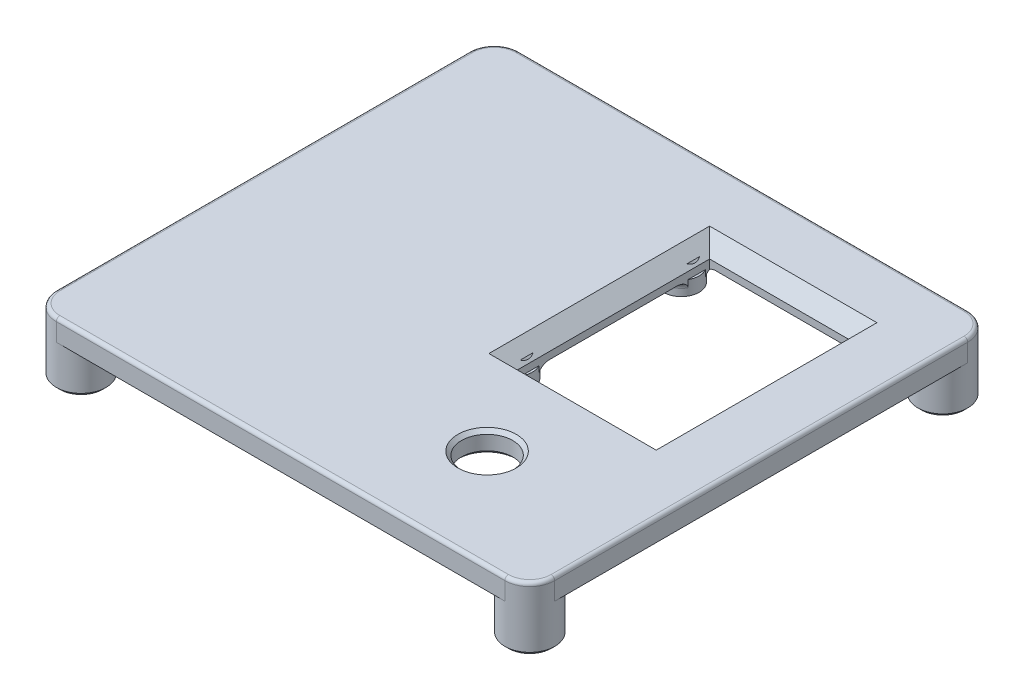
SolidWorks part; units mm, degrees
ref_plane "Front Plane" through (0, 0, 0) normal (0, 0, 1) x (1, 0, 0)
ref_plane "Top Plane" through (0, 0, 0) normal (0, 1, 0) x (1, 0, 0)
ref_plane "Right Plane" through (0, 0, 0) normal (1, 0, 0) x (0, 0, -1)
sketch "Sketch1" plane through (0, 0, 0) normal (0, 1, 0) x (1, 0, 0)
  line L1 (0, 0) -> (70, 0)
  line L2 (0, 0) -> (0, 65)
  line L3 (0, 65) -> (70, 65)
  line L4 (70, 0) -> (70, 65)
  dimension "D1" = 70
  dimension "D2" = 65
extrude "Boss-Extrude1" add sketch "Sketch1" along normal blind 3
fillet "Fillet1" radius 3.5 4 edges at (70, 1.5, -65) (70, 1.5, 0) (0, 1.5, 0) (0, 1.5, -65)
sketch "Sketch2" plane through (0, 0, 0) normal (0, -1, 0) x (1, 0, 0)
  line L0 (35, 0) -> (35, -65) construction
  line L1 (3.5, 0) -> (66.5, 0) construction
  line L2 (66.5, -65) -> (3.5, -65) construction
  line L3 (0, -32.5) -> (70, -32.5) construction
  line L4 (0, -61.5) -> (0, -3.5) construction
  line L5 (70, -3.5) -> (70, -61.5) construction
  circle A0 centre (3.5, -61.5) radius 3.5
  dimension "D1" = 7
extrude "Boss-Extrude2" add sketch "Sketch2" along normal blind 6
sketch "Sketch5" plane through (0, -6, 0) normal (0, -1, 0) x (1, 0, 0)
  circle A0 centre (3.5, -61.5) radius 2
  dimension "D1" = 4
extrude "Cut-Extrude1" cut sketch "Sketch5" against normal blind 5.5 contours A0
chamfer "Chamfer1" distance 0.5 angle 45 2 edges at (3.5, -6, -63.5) (3.5, -6, -65)
pattern_linear "LPattern1" count 2 spacing 63 along (1, 0, 0) count 2 spacing 58 along (0, 0, 1) of "Boss-Extrude2", "Cut-Extrude1", "Chamfer1"
sketch "Sketch6" plane through (0, 0, 0) normal (0, -1, 0) x (1, 0, 0)
  line L0 (0, -61.5) -> (0, -3.5) construction
  line L1 (10, -15) -> (23.7, -15) construction
  line L2 (23.7, -15) -> (16.85, -15) construction
  line L3 (16.85, -15) -> (16.85, -43.3821) construction
  line L4 (3.5, 0) -> (66.5, 0) construction
  circle A0 centre (10, -15) radius 2.5
  circle A1 centre (23.7, -15) radius 2.5
  circle A2 centre (16.85, -43.3821) radius 2.5
  circle A3 centre (10, -15) radius 1
  circle A4 centre (23.7, -15) radius 1
  circle A5 centre (16.85, -43.3821) radius 1
  dimension "D1" = 10
  dimension "D2" = 13.7
  dimension "D3" = 28.3821
  dimension "D4" = 15
extrude "Boss-Extrude3" add sketch "Sketch6" along normal blind 5
fillet "Fillet2" radius 3 3 edges at (16.85, 0, -45.8821) (23.7, 0, -17.5) (10, 0, -17.5)
chamfer "Chamfer2" distance 0.25 angle 45 3 edges at (16.85, -5, -44.3821) (23.7, -5, -16) (10, -5, -16)
chamfer "Chamfer3" distance 0.5 angle 45 3 edges at (16.85, -5, -45.8821) (23.7, -5, -17.5) (10, -5, -17.5)
sketch "Sketch7" plane through (0, 0, 0) normal (0, -1, 0) x (1, 0, 0)
  line L0 (3.5, 0) -> (66.5, 0) construction
  line L1 (0, -61.5) -> (0, -3.5) construction
  line L2 (50, -14) -> (50, 25.0689) construction
  line L3 (40.25, -28) -> (59.75, -28)
  line L4 (40.25, -28) -> (40.25, -55)
  line L5 (40.25, -55) -> (59.75, -55)
  line L6 (59.75, -28) -> (59.75, -55)
  line L7 (50, -28) -> (50, -55) construction
  circle A0 centre (50, -14) radius 3.6
  dimension "D1" = 14
  dimension "D2" = 50
  dimension "D3" = 27
  dimension "D4" = 19.5
  dimension "D5" = 28
extrude "Cut-Extrude2" cut sketch "Sketch7" against normal through all
chamfer "Chamfer4" distance 0.5 angle 45 2 edges at (50, 0, -17.6) (50, 3, -17.6)
chamfer "Chamfer5" distance 2 angle 45 4 edges at (50, 3, -28) (59.75, 3, -41.5) (50, 3, -55) (40.25, 3, -41.5)
sketch "Sketch8" plane through (0, 0, 0) normal (0, -1, 0) x (1, 0, 0)
  line L0 (38.075, -53.2) -> (38.075, -29.8) construction
  line L1 (50, -28) -> (50, -55) construction
  line L3 (59.75, -28) -> (40.25, -28) construction
  line L4 (40.25, -55) -> (59.75, -55) construction
  line L5 (40.25, -41.5) -> (59.75, -41.5) construction
  line L8 (61.925, -29.8) -> (61.925, -53.2) construction
  line L9 (40.25, -28) -> (40.25, -55) construction
  line L10 (59.75, -55) -> (59.75, -28) construction
  line L11 (38.075, -41.5) -> (61.925, -41.5) construction
  line L12 (50, -41.5) -> (50, -27.1029) construction
  circle A0 centre (38.075, -53.2) radius 2.5
  circle A1 centre (61.925, -53.2) radius 2.5
  circle A2 centre (61.925, -29.8) radius 2.5
  circle A3 centre (38.075, -29.8) radius 2.5
  dimension "D1" = 23.85
  dimension "D2" = 23.4
extrude "Boss-Extrude4" add sketch "Sketch8" along normal blind 2
fillet "Fillet5" radius 1 4 edges at (64.425, 0, -53.2) (64.425, 0, -29.8) (35.575, 0, -53.2) (35.575, 0, -29.8)
sketch "Sketch9" plane through (0, -2, 0) normal (0, -1, 0) x (1, 0, 0)
  circle A0 centre (38.075, -29.8) radius 1.9
  circle A1 centre (61.925, -29.8) radius 1.9
  circle A2 centre (38.075, -53.2) radius 1.9
  circle A3 centre (61.925, -53.2) radius 1.9
extrude "Cut-Extrude3" cut sketch "Sketch9" against normal blind 3.5
chamfer "Chamfer6" distance 0.25 angle 45 4 edges at (61.925, -2, -31.7) (38.075, -2, -55.1) (38.075, -2, -31.7) (61.925, -2, -55.1)
fillet "Fillet6" radius 0.5 8 edges at (1.0251, 3, -63.9749) (0, 3, -32.5) (1.0251, 3, -1.0251) (35, 3, 0) (68.9749, 3, -1.0251) (70, 3, -32.5) (68.9749, 3, -63.9749) (35, 3, -65)
